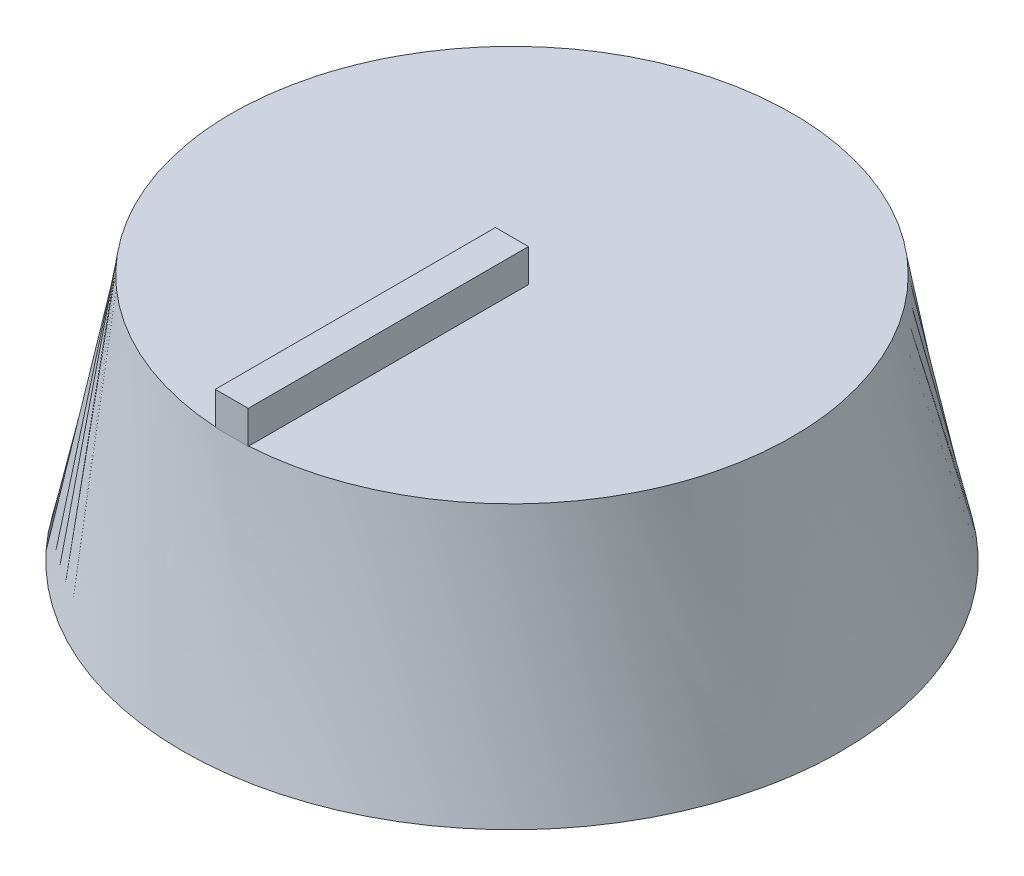
SolidWorks part; units mm, degrees
material "ABS"
ref_plane "Front Plane" through (0, 0, 0) normal (0, 0, 1) x (1, 0, 0)
ref_plane "Top Plane" through (0, 0, 0) normal (0, 1, 0) x (1, 0, 0)
ref_plane "Right Plane" through (0, 0, 0) normal (1, 0, 0) x (0, 0, -1)
sketch "Sketch1" plane through (0, 0, 0) normal (0, 1, 0) x (1, 0, 0)
  circle A0 centre (0, 0) radius 20
  dimension "D1" = 40
ref_plane "Plane1" through (0, 15, 0) normal (0, 1, 0) x (1, 0, 0)
sketch "Sketch2" plane through (0, 15, 0) normal (0, 1, 0) x (1, 0, 0)
  circle A0 centre (0, 0) radius 17
  dimension "D1" = 34
loft "Loft1" add profiles "Sketch1", "Sketch2" connector at (19.8546, 0, -2.4069) connector at (16.799, 15, 2.6066)
sketch "Sketch3" plane through (0, 15, 0) normal (0, 1, 0) x (1, 0, 0)
  line L0 (0, 0) -> (0, -17)
  circle A0 centre (0, 0) radius 17 construction
extrude "Extrude-Thin1" add sketch "Sketch3" along normal blind 2 thin thin type mid plane wall 2
